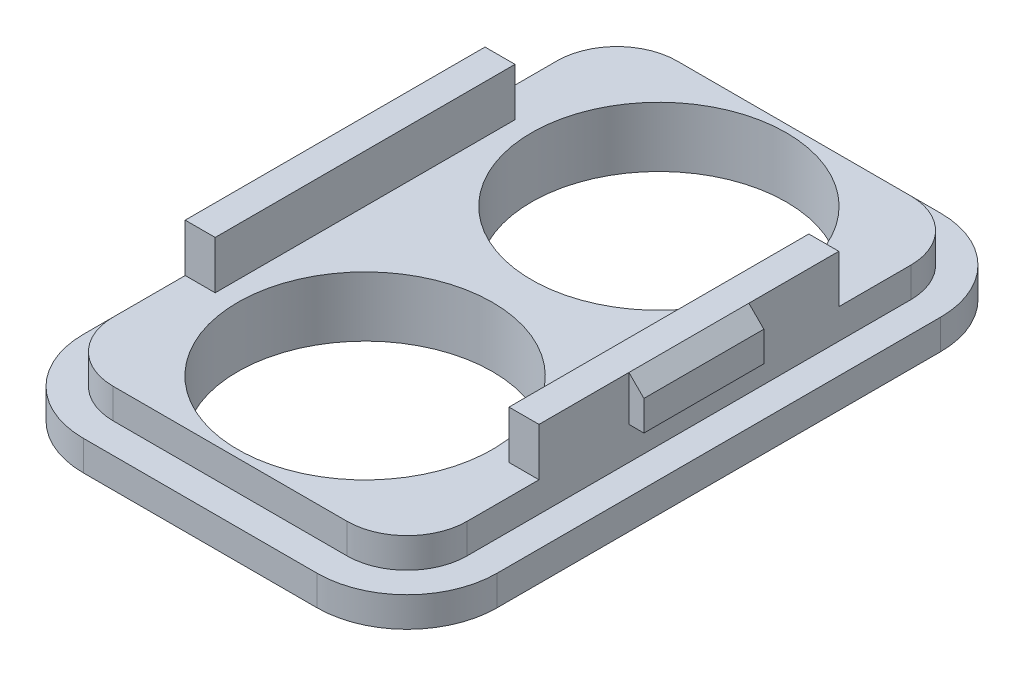
SolidWorks part; units mm, degrees
ref_plane "前视基准面" through (0, 0, 0) normal (0, 0, 1) x (1, 0, 0)
ref_plane "上视基准面" through (0, 0, 0) normal (0, 1, 0) x (1, 0, 0)
ref_plane "右视基准面" through (0, 0, 0) normal (1, 0, 0) x (0, 0, -1)
other "Configuration Table"
sketch "草图1" plane through (0, 0, 0) normal (0, 1, 0) x (1, 0, 0)
  line L1 (2, 0) -> (9.8, 0)
  line L2 (0, 2) -> (0, 16.8)
  line L3 (2, 18.8) -> (9.8, 18.8)
  line L4 (11.8, 2) -> (11.8, 16.8)
  line L5 (0, 0) -> (11.8, 18.8) construction
  line L6 (0, 18.8) -> (11.8, 0) construction
  arc A0 (0, 16.8) -> (2, 18.8) centre (2, 16.8) cw
  arc A1 (11.8, 16.8) -> (9.8, 18.8) centre (9.8, 16.8) ccw
  arc A2 (9.8, 0) -> (11.8, 2) centre (9.8, 2) ccw
  arc A3 (2, 0) -> (0, 2) centre (2, 2) cw
  point P4 (5.9, 9.4)
  dimension "D3" = 2
  dimension "D1" = 11.8
  dimension "D2" = 18.8
extrude "凸台-拉伸1" add sketch "草图1" along normal blind 1
sketch "草图2" plane through (0, 1, 0) normal (0, 1, 0) x (1, 0, 0)
  line L0 (0, 16.8) -> (0, 2) construction
  line L1 (0, 14.4) -> (1, 14.4)
  line L2 (0, 14.4) -> (0, 4.4)
  line L3 (0, 4.4) -> (1, 4.4)
  line L4 (1, 14.4) -> (1, 4.4)
  line L5 (0, 14.4) -> (1, 4.4) construction
  line L6 (0, 4.4) -> (1, 14.4) construction
  line L7 (5.9, 18.8) -> (5.9, 0) construction
  line L8 (9.8, 18.8) -> (2, 18.8) construction
  line L9 (2, 0) -> (9.8, 0) construction
  line L10 (0.5, 9.4) -> (5.9, 9.4) construction
  line L11 (11.8, 4.4) -> (10.8, 14.4) construction
  line L12 (11.8, 14.4) -> (10.8, 4.4) construction
  line L13 (10.8, 14.4) -> (10.8, 4.4)
  line L14 (11.8, 4.4) -> (10.8, 4.4)
  line L15 (11.8, 14.4) -> (11.8, 4.4)
  line L16 (11.8, 14.4) -> (10.8, 14.4)
  point P4 (0.5, 9.4)
  point P19 (11.3, 9.4)
  dimension "D1" = 10
  dimension "D2" = 1
extrude "凸台-拉伸2" add sketch "草图2" along normal blind 1.6
ref_plane "基准面1" through (0, 0, -9.4) normal (0, 0, 1) x (1, 0, 0)
sketch "草图3" plane through (0, 0, -9.4) normal (0, 0, 1) x (1, 0, 0)
  line L0 (0, 2.6) -> (0, 1.1)
  line L1 (0, 2.6) -> (0, 1) construction
  line L2 (0, 1.1) -> (-0.5, 1.1)
  line L3 (-0.5, 1.1) -> (-0.5, 2.1)
  line L4 (-0.5, 2.1) -> (0, 2.6)
  point P5 (0, 1.5851)
  dimension "D1" = 135
  dimension "D2" = 0.5
  dimension "D3" = 1
extrude "凸台-拉伸3" add sketch "草图3" along normal blind 2 and the other way blind 2
sketch "草图4" plane through (0, 0, 0) normal (0, -1, 0) x (1, 0, 0)
  line L8 (2, -19.8) -> (9.8, -19.8)
  line L9 (12.8, -16.8) -> (12.8, -2)
  line L10 (9.8, 1) -> (2, 1)
  line L11 (-1, -2) -> (-1, -16.8)
  line L12 (2, -19.8) -> (9.8, -19.8)
  line L13 (12.8, -16.8) -> (12.8, -2)
  line L14 (9.8, 1) -> (2, 1)
  line L15 (-1, -2) -> (-1, -16.8)
  arc A8 (-1, -16.8) -> (2, -19.8) centre (2, -16.8) ccw
  arc A9 (9.8, -19.8) -> (12.8, -16.8) centre (9.8, -16.8) ccw
  arc A10 (12.8, -2) -> (9.8, 1) centre (9.8, -2) ccw
  arc A11 (2, 1) -> (-1, -2) centre (2, -2) ccw
  arc A12 (-1, -16.8) -> (2, -19.8) centre (2, -16.8) ccw
  arc A13 (9.8, -19.8) -> (12.8, -16.8) centre (9.8, -16.8) ccw
  arc A14 (12.8, -2) -> (9.8, 1) centre (9.8, -2) ccw
  arc A15 (2, 1) -> (-1, -2) centre (2, -2) ccw
  dimension "D1" = 1
extrude "凸台-拉伸4" add sketch "草图4" along normal blind 1
ref_plane "基准面2" through (5.9, 0, 0) normal (-1, 0, 0) x (0, 0, 1)
mirror "镜向1" about plane through (0, 0, -9.4) normal (0, 0, 1) of "凸台-拉伸3" second plane through (5.9, 0, 0) second plane normal (-1, 0, 0)
sketch "草图5" plane through (0, -1, 0) normal (0, -1, 0) x (1, 0, 0)
  circle A0 centre (5.9, -4.5) radius 4.25
  circle A1 centre (5.9, -14.3) radius 4.25
  dimension "D1" = 8.5
extrude "切除-拉伸1" cut sketch "草图5" against normal through all
